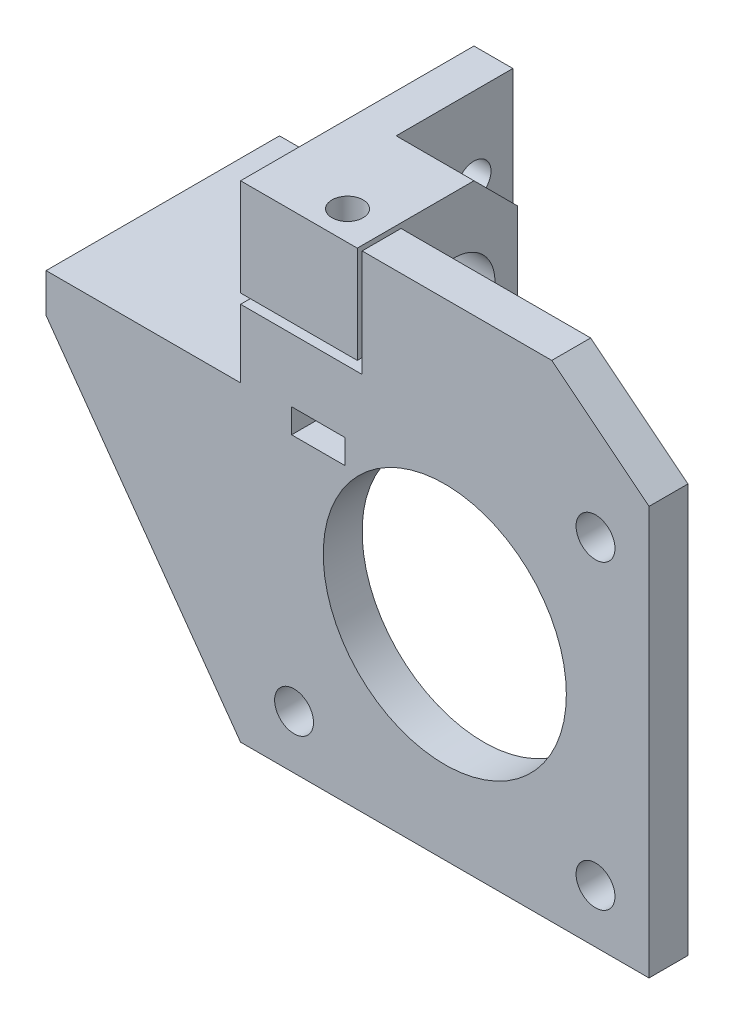
SolidWorks part; units mm, degrees
ref_plane "Plano frontal" through (0, 0, 0) normal (0, 0, 1) x (1, 0, 0)
ref_plane "Plano superior" through (0, 0, 0) normal (0, 1, 0) x (1, 0, 0)
ref_plane "Plano direito" through (0, 0, 0) normal (1, 0, 0) x (0, 0, -1)
sketch "Esboço1" plane through (0, 0, 0) normal (0, 0, 1) x (1, 0, 0)
  line L3 (-49.7252, 0) -> (0, 0) construction
  line L18 (-15.5, 15.5) -> (15.5, -15.5) construction
  line L19 (-15.5, -15.5) -> (15.5, 15.5) construction
  line L20 (15.5, -15.5) -> (15.5, 15.5) construction
  line L21 (-15.5, 15.5) -> (15.5, 15.5) construction
  line L22 (-15.5, -15.5) -> (-15.5, 15.5) construction
  line L23 (-15.5, -15.5) -> (15.5, -15.5) construction
  line L24 (-21, 21) -> (21, -21) construction
  line L25 (-21, -21) -> (21, 21) construction
  line L26 (-41, 7) -> (-21, -21)
  line L27 (11, 29) -> (21, 21)
  line L28 (-21, 29) -> (11, 29)
  line L29 (-21, 21) -> (-21, 29)
  line L30 (-41, 11) -> (-41, 7)
  line L31 (21, -21) -> (21, 21)
  line L32 (-21, 11) -> (-21, 21)
  line L33 (-21, -21) -> (21, -21)
  line L34 (-21, 11) -> (-41, 11)
  circle A3 centre (0, 0) radius 12.5
  circle A4 centre (15.5, 15.5) radius 2
  circle A5 centre (15.5, -15.5) radius 2
  circle A6 centre (-15.5, -15.5) radius 2
  point P0 (0, 0)
  point P3 (0, -15.5)
  point P4 (15.5, 0)
  point P6 (0, 0)
  point P16 (0, 0)
  dimension "D2" = 42
  dimension "D5" = 25
  dimension "D3" = 4
  dimension "D1" = 31
  dimension "D4" = 8
  dimension "D6" = 10
  dimension "D7" = 32
  dimension "D8" = 20
  dimension "D9" = 18
  dimension "D10" = 28
extrude "Ressalto-extrusão1" add sketch "Esboço1" along normal blind 4
sketch "Esboço2" plane through (0, 0, 0) normal (0, 0, -1) x (-1, 0, 0)
  line L0 (41, 11) -> (41, 7)
  line L1 (41, 7) -> (21, 7)
  line L2 (17, 11) -> (17, 29)
  line L3 (-11, 29) -> (21, 29) construction
  line L4 (17, 29) -> (21, 29)
  line L5 (21, 29) -> (21, 11)
  line L6 (21, 11) -> (41, 11)
  line L7 (21, 11) -> (41, 11) construction
  line L8 (41, 11) -> (41, 7) construction
  line L9 (41, 7) -> (21, -21) construction
  line L10 (21, 29) -> (21, 11) construction
  arc A0 (17, 11) -> (21, 7) centre (21, 11) ccw
extrude "Ressalto-extrusão2" add sketch "Esboço2" along normal blind 20
sketch "Esboço3" plane through (-17, 0, 0) normal (1, 0, 0) x (0, 0, -1)
  line L0 (0, 29) -> (8, 29)
  line L2 (8, 29) -> (12.5, 24.5)
  line L3 (12.5, 24.5) -> (12.5, 13.5)
  line L4 (12.5, 13.5) -> (8, 9)
  line L5 (20, 29) -> (0, 29) construction
  line L6 (8, 9) -> (0, 9)
  line L7 (0, 9) -> (0, 29)
  line L9 (8, 29) -> (8, 9) construction
  line L10 (0, 29) -> (0, 11) construction
  circle A0 centre (6, 19) radius 4.15
  point P6 (12.5, 19)
  dimension "D1" = 8.3
  dimension "D2" = 6
  dimension "D3" = 20
  dimension "D4" = 11
  dimension "D5" = 2
extrude "Ressalto-extrusão3" add sketch "Esboço3" along normal blind 8
sketch "Esboço4" plane through (0, 0, 0) normal (0, 0, -1) x (-1, 0, 0)
  line L0 (9, 19) -> (26.3177, 19)
  line L1 (-11, 29) -> (9, 29) construction
  line L2 (9, 24.5) -> (9, 29) construction
  line L3 (26.3177, 19) -> (26.3177, 15.2911)
  line L4 (26.3177, 15.2911) -> (25.8177, 15.2911)
  line L5 (9, 9) -> (17, 9) construction
  line L6 (25.8177, 15.2911) -> (25.8177, 18)
  line L7 (25.8177, 18) -> (8.5, 18)
  line L8 (8.5, 18) -> (8.5, 29)
  line L9 (8.5, 29) -> (9, 29)
  line L10 (9, 29) -> (9, 19)
  line L11 (9, 9) -> (17, 9) construction
  line L12 (15.75, 11.5) -> (10.25, 11.5)
  line L13 (15.75, 11.5) -> (15.75, 9)
  line L14 (15.75, 9) -> (10.25, 9)
  line L15 (10.25, 11.5) -> (10.25, 9)
  line L16 (15.75, 11.5) -> (10.25, 9) construction
  line L17 (15.75, 9) -> (10.25, 11.5) construction
  point P16 (13, 9)
  point P26 (13, 10.25)
  dimension "D1" = 10
  dimension "D2" = 1
  dimension "D3" = 0.5
  dimension "D4" = 0.5
  dimension "D5" = 2.5
  dimension "D6" = 5.5
extrude "Corte-extrusão1" cut sketch "Esboço4" against normal blind 8 and the other way blind 3
sketch "Esboço5" plane through (-17, 0, 0) normal (1, 0, 0) x (0, 0, -1)
  line L1 (20, 11) -> (20, 29) construction
  line L2 (20, 11) -> (10, 11) construction
  circle A0 centre (16, 21) radius 1.75
  circle A2 centre (6, 19) radius 4.15
  dimension "D3" = 3.5
  dimension "D1" = 10
  dimension "D2" = 4
extrude "Corte-extrusão2" cut sketch "Esboço5" against normal blind 12
sketch "Esboço6" plane through (0, 7, 0) normal (0, -1, 0) x (-1, 0, 0)
  line L1 (21, 20) -> (41, 20) construction
  line L2 (21, 20) -> (21, 0) construction
  circle A0 centre (31.5, 13) radius 1.75
  circle A1 centre (31.5, -7) radius 1.75
  dimension "D2" = 3.5
  dimension "D1" = 20
  dimension "D3" = 10.5
  dimension "D4" = 7
extrude "Corte-extrusão3" cut sketch "Esboço6" against normal blind 12
sketch "Esboço7" plane through (0, 9, 0) normal (0, -1, 0) x (1, 0, 0)
  line L0 (-9, -8) -> (-17, -8) construction
  line L2 (-9, 0) -> (-10.25, 0) construction
  circle A0 centre (-13, 1) radius 1.6
  point P5 (-13, -8)
  dimension "D2" = 3.2
  dimension "D1" = 1
extrude "Corte-extrusão4" cut sketch "Esboço7" against normal through all
